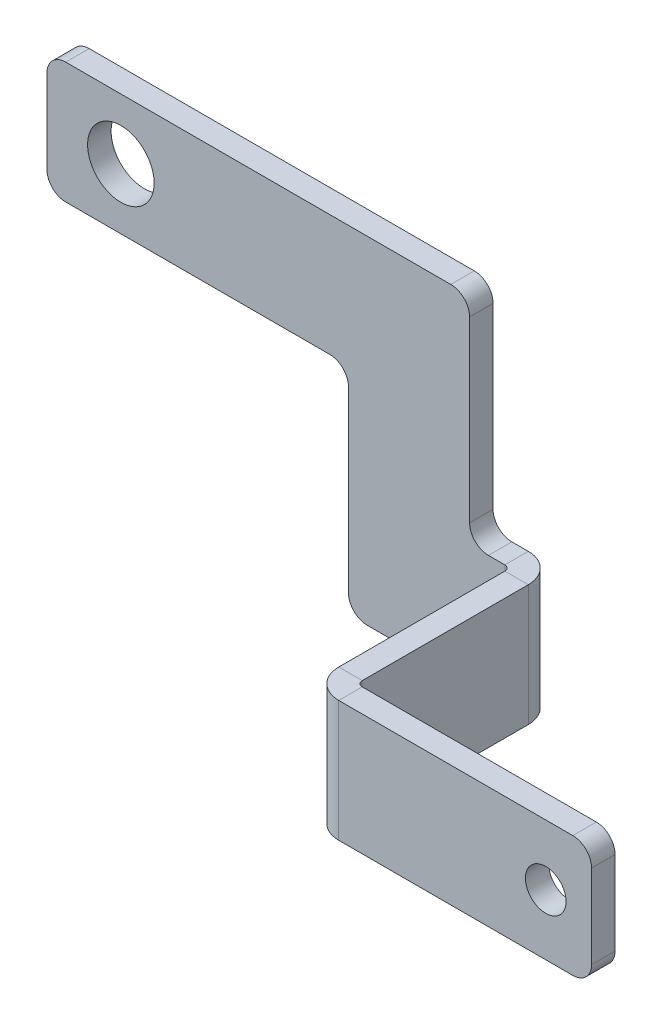
SolidWorks part; units mm, degrees
note: The reader was unsure of these and kept them because the rebuilt part matched: flange length of "Edge-Flange1", "Edge-Flange2".
material "3003-H14"
ref_plane "X-Y Datum" through (0, 0, 0) normal (0, 0, 1) x (1, 0, 0)
ref_plane "X-Z Datum" through (0, 0, 0) normal (0, 1, 0) x (1, 0, 0)
ref_plane "Y-Z Datum" through (0, 0, 0) normal (1, 0, 0) x (0, 0, -1)
sketch "Sketch1" plane through (0, 0, 0) normal (0, 0, 1) x (1, 0, 0)
  line L0 (0, -8.189) -> (57.15, -8.189) construction
  line L1 (0, 0) -> (57.15, 0)
  line L2 (0, 0) -> (0, -16.378)
  line L3 (0, -16.378) -> (40.772, -16.378)
  line L4 (57.15, 0) -> (57.15, -16.378)
  line L5 (61.9125, -37.3736) -> (56.0244, -37.3736) construction
  line L7 (57.15, -16.378) -> (57.15, -29.1846)
  line L8 (57.15, -45.5626) -> (40.772, -45.5626)
  line L9 (40.772, -16.378) -> (40.772, -45.5626)
  line L10 (57.15, -45.5626) -> (61.9125, -45.5626)
  line L12 (57.15, -29.1846) -> (61.9125, -29.1846)
  line L13 (61.9125, -45.5626) -> (61.9125, -29.1846)
  line L14 (88.5359, -37.3736) -> (100.5639, -37.3736) construction
  circle A0 centre (10, -8.189) radius 4 construction
  point P9 (94.5499, -37.3736)
  point P26 (94.5499, -37.3736)
  dimension "D3" = 8
  dimension "D1" = 16.378
  dimension "D2" = 57.15
  dimension "D4" = 10
  dimension "D5" = 4.7625
base flange "Base-Flange1" sketch "Sketch1" thickness 3.175 reverse thickness direction no parameters "D1"=0.7366
hole_wizard "M8 Clearance Hole1" positions "Sketch6" profile "Sketch7" hole size "M8" standard "ANSI Metric" end condition through all
sketch "Sketch6" plane through (0, 0, 0) normal (0, 0, 1) x (1, 0, 0)
  point P0 (10, -8.189)
sketch "Sketch7" plane through (10, -8.189, 0) normal (1, 0, 0) x (0, -1, 0)
  line L0 (0, 0) -> (0, 3.175)
  line L1 (0, 3.175) -> (4.5, 3.175)
  line L2 (4.5, 3.175) -> (4.5, 0)
  line L5 (4.5, 0) -> (0, 0)
  line L11 (0, -6.35) -> (0, 107.95) construction
  dimension "Thru Hole Dia." = 9
  dimension "Thru Hole Depth" = 3.175
edge flange "Edge-Flange1" sketch "Sketch12" flange angle 90 flange length 23.9268 flange position bend outside bend radius 0.7366 thickness 3.175 relief rectangular parameters "D6"=10
sketch "Sketch12" plane through (61.9125, 0, 0) normal (1, 0, 0) x (0, 1, 0)
  line L0 (-45.5626, 0) -> (-29.1846, 0) construction
  line L1 (-45.5626, 0) -> (-29.1846, 0)
  line L2 (-45.5626, 0) -> (-45.5626, 23.9268)
  line L3 (-45.5626, 23.9268) -> (-29.1846, 23.9268)
  line L4 (-29.1846, 23.9268) -> (-29.1846, 0)
bend "EdgeBend1" bend radius 0.7366 bend angle 90 parameters "D5"=1
edge flange "Edge-Flange2" sketch "Sketch15" flange angle 90 flange length 38.1 flange position material outside bend radius 0.7366 thickness 3.175 relief rectangular parameters "D6"=10
sketch "Sketch15" plane through (65.8241, 0, 23.9268) normal (0, 0, 1) x (0, -1, 0)
  line L0 (29.1846, 0) -> (45.5626, 0) construction
  line L1 (29.1846, 0) -> (45.5626, 0)
  line L2 (29.1846, 0) -> (29.1846, 34.925)
  line L3 (29.1846, 34.925) -> (45.5626, 34.925)
  line L4 (45.5626, 34.925) -> (45.5626, 0)
bend "EdgeBend2" bend radius 0.7366 bend angle 90 parameters "D5"=2
sketch "Sketch16" plane through (0, 0, 27.1018) normal (0, 0, 1) x (1, 0, 0)
  point P0 (94.5499, -37.3736)
hole_wizard "M5 Clearance Hole1" positions "Sketch17" profile "Sketch18" hole size "M5" standard "ANSI Metric" end condition through all
sketch "Sketch17" plane through (0, 0, 27.1018) normal (0, 0, 1) x (1, 0, 0)
  point P0 (94.5499, -37.3736)
  point P3 (94.5499, -37.3736)
  point P5 (94.5499, -37.3736)
sketch "Sketch18" plane through (94.5499, -37.3736, 27.1018) normal (1, 0, 0) x (0, -1, 0)
  line L0 (0, 0) -> (0, 30.2768)
  line L1 (0, 30.2768) -> (2.75, 30.2768)
  line L2 (2.75, 30.2768) -> (2.75, 0)
  line L5 (2.75, 0) -> (0, 0)
  line L11 (0, -6.35) -> (0, 107.95) construction
  dimension "Thru Hole Dia." = 5.5
  dimension "Thru Hole Depth" = 30.2768
fillet "Fillet1" radius 2.54 8 edges at (40.772, -16.378, -1.5875) (100.7491, -29.1846, 25.5143) (100.7491, -45.5626, 25.5143) (0, -16.378, -1.5875) (0, 0, -1.5875) (57.15, 0, -1.5875) (57.15, -29.1846, -1.5875) (40.772, -45.5626, -1.5875)
sketch "Bend-Lines1" [suppressed] plane through (0, 0, 0) normal (0, 1, 0) x (1, 0, 0)
sketch "Bounding-Box1" [suppressed] plane through (0, 0, 0) normal (0, 1, 0) x (1, 0, 0)
sheet metal parameters "Sheet-Metal3" thickness 3.175 parameters "D1"=0.7366
flat pattern "Flat-Pattern3" [suppressed]
sketch "Bend-Lines2" plane through (0, 0, 0) normal (0, 1, 0) x (1, 0, 0)
sketch3d "Bounding-Box2" [suppressed]
  line L0 (0, -16.378, 0) -> (-76.2, -16.378, 0) construction
  line L1 (0, 0, 0) -> (-76.2, 0, 0) construction
  line L2 (0, -16.378, 0) -> (0, 0, 0) construction
  line L3 (-76.2, -16.378, 0) -> (-76.2, 0, 0) construction
sheet metal parameters "Sheet-Metal4" thickness 3.175 parameters "D1"=0.7366
flat pattern "Flat-Pattern3"
sketch "Bend-Lines2" plane through (0, 0, 0) normal (0, 1, 0) x (1, 0, 0)
sketch3d "Bounding-Box2" [suppressed]
  line L0 (0, -16.378, 0) -> (76.2, -16.378, 0) construction
  line L1 (0, 0, 0) -> (76.2, 0, 0) construction
  line L2 (0, -16.378, 0) -> (0, 0, 0) construction
  line L3 (76.2, -16.378, 0) -> (76.2, 0, 0) construction
sheet metal parameters "Sheet-Metal5" thickness 3.175 parameters "D1"=0.7366
flat pattern "Flat-Pattern3"
sketch "Bend-Lines2" plane through (0, 0, 0) normal (0, 0, 1) x (1, 0, 0)
  line L0 (62.1503, -45.5626) -> (62.1503, -29.1846) construction
  line L1 (62.1503, -45.5626) -> (62.1503, -29.1846) construction
sketch3d "Bounding-Box2" [suppressed]
  line L0 (0, -45.5626, 0) -> (87.1659, -45.5626, 0) construction
  line L1 (0, 0, 0) -> (87.1659, 0, 0) construction
  line L2 (0, -45.5626, 0) -> (0, 0, 0) construction
  line L3 (87.1659, -45.5626, 0) -> (87.1659, 0, 0) construction
bend of the flat pattern "Flatten-<EdgeBend1>1"
sheet metal parameters "Sheet-Metal6" thickness 3.175 parameters "D1"=0.7366
flat pattern "Flat-Pattern3"
sketch "Bend-Lines2" plane through (0, 0, 0) normal (0, 0, 1) x (1, 0, 0)
  line L0 (62.1503, -45.5626) -> (62.1503, -29.1846) construction
  line L1 (62.1503, -45.5626) -> (62.1503, -29.1846) construction
  line L2 (88.2546, -45.5626) -> (88.2546, -29.1846) construction
  line L3 (88.2546, -45.5626) -> (88.2546, -29.1846) construction
sketch3d "Bounding-Box2" [suppressed]
  line L0 (0, -45.5626, 0) -> (125.5384, -45.5626, 0) construction
  line L1 (0, 0, 0) -> (125.5384, 0, 0) construction
  line L2 (0, -45.5626, 0) -> (0, 0, 0) construction
  line L3 (125.5384, -45.5626, 0) -> (125.5384, 0, 0) construction
bend of the flat pattern "Flatten-<EdgeBend1>1"
bend of the flat pattern "Flatten-<EdgeBend2>1"
sheet metal parameters "Sheet-Metal7" thickness 3.175 parameters "D1"=0.7366
flat pattern "Flat-Pattern3" [suppressed]
sketch "Bend-Lines2" plane through (0, 0, 0) normal (0, 0, 1) x (1, 0, 0)
  line L0 (63.7378, -45.5626) -> (63.7378, -29.1846) construction
  line L1 (63.7378, -45.5626) -> (63.7378, -29.1846) construction
  line L2 (89.8421, -45.5626) -> (89.8421, -29.1846) construction
  line L3 (89.8421, -45.5626) -> (89.8421, -29.1846) construction
sketch3d "Bounding-Box2" [suppressed]
  line L0 (0, -45.5626, 0) -> (125.8559, -45.5626, 0) construction
  line L1 (0, 0, 0) -> (125.8559, 0, 0) construction
  line L2 (0, -45.5626, 0) -> (0, 0, 0) construction
  line L3 (125.8559, -45.5626, 0) -> (125.8559, 0, 0) construction
bend of the flat pattern "Flatten-<EdgeBend1>1"
bend of the flat pattern "Flatten-<EdgeBend2>1"
sketch "Sketch16-1" [suppressed] plane through (25.1068, 0, 0) normal (0, 0, 1) x (1, 0, 0)
  point P0 (94.5499, -37.3736)
